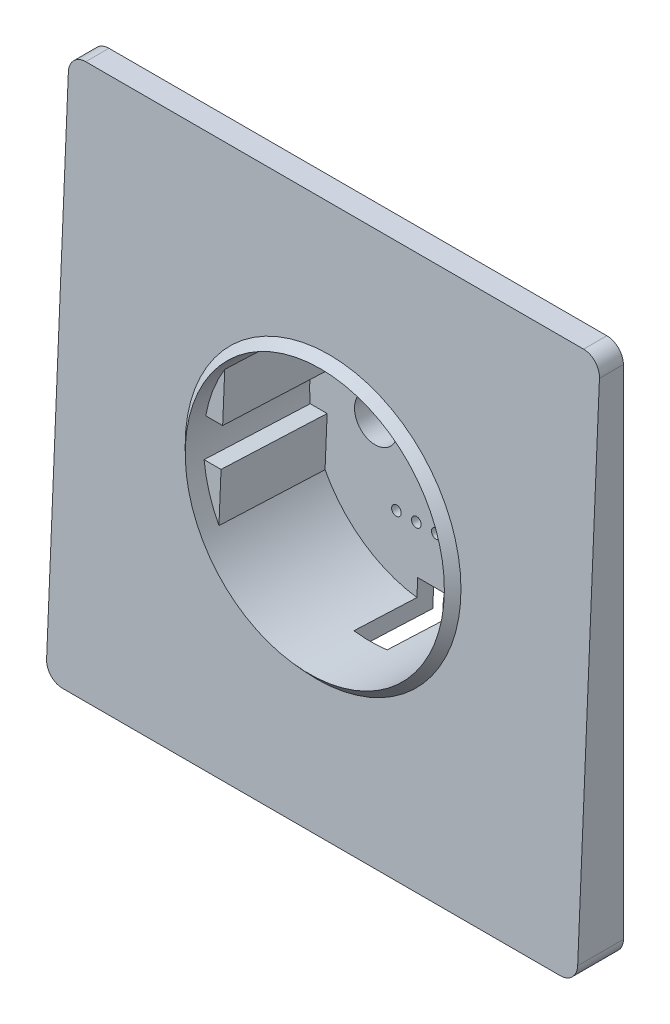
SolidWorks part; units mm, degrees
ref_plane "Ön Düzlem" through (0, 0, 0) normal (0, 0, 1) x (1, 0, 0)
ref_plane "Üst Düzlem" through (0, 0, 0) normal (0, 1, 0) x (1, 0, 0)
ref_plane "Sağ Düzlem" through (0, 0, 0) normal (1, 0, 0) x (0, 0, -1)
sketch "Çizim1" plane through (0, 0, 0) normal (0, 0, 1) x (1, 0, 0)
  line L0 (0, 94.0978) -> (0, -81.5347) construction
  line L1 (-96.2335, 0) -> (117.8421, 0) construction
  line L3 (-37.5, 40) -> (37.5, 40)
  line L4 (-40, 37.5) -> (-40, -37.5)
  line L5 (-37.5, -40) -> (37.5, -40)
  line L6 (40, 37.5) -> (40, -37.5)
  arc A0 (-40, -37.5) -> (-37.5, -40) centre (-37.5, -37.5) ccw
  arc A1 (37.5, -40) -> (40, -37.5) centre (37.5, -37.5) ccw
  arc A2 (37.5, 40) -> (40, 37.5) centre (37.5, 37.5) cw
  arc A3 (-37.5, 40) -> (-40, 37.5) centre (-37.5, 37.5) ccw
  point P17 (-40, 40)
  dimension "D5" = 2.5
  dimension "D1" = 40
  dimension "D2" = 80
  dimension "D3" = 80
  dimension "D4" = 40
extrude "Ekstrüzyon-İnce3" add sketch "Çizim1" along normal blind 7 thin thin type one direction reverse wall 2.5
sketch "Çizim6" plane through (40, 0, 0) normal (1, 0, 0) x (0, 0, -1)
  line L1 (-7, 40) -> (0, 40) construction
  line L2 (-3.5, 40) -> (-7, -40)
  line L3 (-7, -40) -> (-7, 40)
  line L4 (-7, 40) -> (-3.5, 40)
  dimension "D1" = 3.5
extrude "Kes-Ekstrüzyon3" cut sketch "Çizim6" against normal blind 112.5
sketch "Çizim7" plane through (0, 0.2292, 5.24) normal (0, 0.0437, 0.999) x (1, 0, 0)
  line L1 (-38.2758, 38.3418) -> (38.3792, 38.3418)
  line L2 (-38.2758, 38.3418) -> (-38.2758, -38.4901)
  line L3 (-38.2758, -38.4901) -> (38.3792, -38.4901)
  line L4 (38.3792, 38.3418) -> (38.3792, -38.4901)
extrude "Yükseklik-Ekstrüzyon15" add sketch "Çizim7" against normal blind 2.5
sketch "Çizim8" plane through (0, 0.2292, 5.24) normal (0, 0.0437, 0.999) x (1, 0, 0)
  line L0 (0, 29.8509) -> (0, -26.0645) construction
  line L1 (-19.0344, 0) -> (24.7241, 0) construction
  circle A0 centre (0, 0) radius 19.5
  dimension "D1" = 39
extrude "Kes-Ekstrüzyon4" cut sketch "Çizim8" against normal blind 17.5
sketch "Çizim9" plane through (0, 0.2292, 5.24) normal (0, 0.0437, 0.999) x (1, 0, 0)
  circle A0 centre (0, 0) radius 20.75
  dimension "D1" = 41.5
extrude "Yükseklik-Ekstrüzyon16" add sketch "Çizim9" against normal blind 17.5
sketch "Çizim10" plane through (0, 0.2292, 5.24) normal (0, 0.0437, 0.999) x (1, 0, 0)
  circle A0 centre (0, 0) radius 19.5
  dimension "D1" = 39
extrude "Kes-Ekstrüzyon5" cut sketch "Çizim10" against normal blind 17.5
sketch "Çizim11" plane through (0, 0.2292, 5.24) normal (0, 0.0437, 0.999) x (1, 0, 0)
  circle A0 centre (0, 0) radius 20.75
  circle A1 centre (0, 0) radius 19.5
  dimension "D1" = 41.5
  dimension "D2" = 39
extrude "Yükseklik-Ekstrüzyon17" add sketch "Çizim11" along normal blind 1.5
chamfer "Pah1" distance 1.5 angle 45 1 edges at (0, -20.4354, 7.6455)
sketch "Çizim12" plane through (0, -0.5356, -12.2433) normal (0, -0.0437, -0.999) x (-1, 0, 0)
  circle A0 centre (0, 0) radius 20.75
  dimension "D1" = 41.5
extrude "Yükseklik-Ekstrüzyon18" add sketch "Çizim12" along normal blind 2.5
sketch "Çizim13" plane through (0, -0.5356, -12.2433) normal (0, 0.0437, 0.999) x (1, 0, 0)
  line L0 (0, 36.6223) -> (0, -26.6449) construction
  line L1 (7.6552, 0) -> (-11.4827, 0) construction
  circle A0 centre (-9.5, 0) radius 3.25
  circle A1 centre (9.5, 0) radius 3.25
  dimension "D2" = 19
  dimension "D3" = 6.5
  dimension "D4" = 6.5
  dimension "D1" = 9.5
extrude "Kes-Ekstrüzyon7" cut sketch "Çizim13" against normal blind 2.5
sketch "Çizim14" plane through (0, -0.5356, -12.2433) normal (0, 0.0437, 0.999) x (1, 0, 0)
  line L0 (0, 29.0101) -> (0, -24.8666) construction
  line L1 (29.1526, 0) -> (-30.9953, 0) construction
  line L2 (19.2979, 2.8) -> (16.75, 2.8)
  line L3 (16.75, 9.9844) -> (16.75, 2.8)
  line L4 (16.75, -9.9844) -> (16.75, -2.8)
  line L5 (-19.2979, 2.8) -> (-16.75, 2.8)
  line L6 (-16.75, 9.9844) -> (-16.75, 2.8)
  line L7 (19.2979, -2.8) -> (16.75, -2.8)
  line L8 (-16.75, -9.9844) -> (-16.75, -2.8)
  line L9 (-19.2979, -2.8) -> (-16.75, -2.8)
  circle A0 centre (0, 0) radius 19.5
  circle A1 centre (0, 0) radius 19.5 construction
  circle M3 centre (0, 0) radius 19.5
  dimension "D1" = 39
  dimension "D2" = 5.6
  dimension "D4" = 33.5
sketch "Çizim15" plane through (0, -0.5356, -12.2433) normal (0, 0.0437, 0.999) x (1, 0, 0)
  line L0 (0, 34.4478) -> (0, -34.2039) construction
  line L1 (-31.9655, 0) -> (33.3103, 0) construction
  line L2 (2.5, -19.3391) -> (2.5, -16.7891)
  line L3 (-2.5, -16.7891) -> (2.5, -16.7891)
  line L4 (-2.5, 19.3391) -> (-2.5, 16.7891)
  line L5 (-2.5, 16.7891) -> (2.5, 16.7891)
  line L6 (2.5, 19.3391) -> (2.5, 16.7891)
  line L7 (-2.5, -19.3391) -> (-2.5, -16.7891)
  arc A0 (16.75, 9.9844) -> (-16.75, 9.9844) centre (0, 0) ccw construction
  circle A1 centre (0, 0) radius 19.5
  arc M7 (16.75, 9.9844) -> (-16.75, 9.9844) centre (0, 0) ccw
  arc M13 (-16.75, -9.9844) -> (16.75, -9.9844) centre (0, 0) ccw
  dimension "D4" = 39
  dimension "D1" = 2.5
  dimension "D2" = 5
  dimension "D3" = 2.55
extrude "Kes-Ekstrüzyon8" cut sketch "Çizim15" against normal blind 16 contours L6 L4 L5 M7 | L7 L2 L3 M13 region at (0, -18.6365, -11.4514) region at (0, 17.5652, -13.0352)
sketch "Çizim16" plane through (0, -0.6449, -14.7409) normal (0, -0.0437, -0.999) x (-1, 0, 0)
  line L0 (2.5, 16.7891) -> (2.5, 19.3391) construction
  line L1 (-2.5, 16.7891) -> (2.5, 16.7891)
  line L2 (-2.5, 16.7891) -> (-2.5, 21.7891)
  line L3 (-2.5, 21.7891) -> (2.5, 21.7891)
  line L4 (2.5, 16.7891) -> (2.5, 21.7891)
  line L5 (0, 9.913) -> (0, -8.6219) construction
  line L6 (-13.1379, 0) -> (18.1034, 0) construction
  line L7 (-2.5, -16.7891) -> (2.5, -16.7891)
  line L8 (-2.5, -16.7891) -> (-2.5, -21.7891)
  line L9 (-2.5, -21.7891) -> (2.5, -21.7891)
  line L10 (2.5, -16.7891) -> (2.5, -21.7891)
  dimension "D1" = 5
extrude "Kes-Ekstrüzyon10" cut sketch "Çizim16" against normal blind 12
sketch "Çizim17" plane through (0, -0.6449, -14.7409) normal (0, -0.0437, -0.999) x (-1, 0, 0)
  line L0 (0, 10.9316) -> (0, -10.3701) construction
  line L1 (-3.5611, 0) -> (5.2947, 0) construction
  line L3 (-7.5, -8.6891) -> (7.5, -8.6891)
  line L4 (-7.5, -8.6891) -> (-7.5, -11.1891)
  line L5 (-7.5, -11.1891) -> (7.5, -11.1891)
  line L6 (7.5, -8.6891) -> (7.5, -11.1891)
  dimension "D1" = 2.5
  dimension "D2" = 15
  dimension "D3" = 7.5
  dimension "D4" = 5.6
extrude "Yükseklik-Ekstrüzyon21" add sketch "Çizim14" along normal blind 16 contours L6 L5 M3 | L9 L8 M3 | L3 L2 M3 | L7 L4 M3 region at (17.6973, 4.8699, -12.4798) region at (17.6973, -5.9412, -12.0068) region at (-17.6973, 4.8699, -12.4798) region at (-17.6973, -5.9412, -12.0068)
extrude "Kes-Ekstrüzyon14" cut sketch "Çizim17" against normal blind 0.5
sketch "Çizim19" plane through (0, -0.6231, -14.2414) normal (0, -0.0437, -0.999) x (-1, 0, 0)
  line L0 (0, 2.2115) -> (0, -5.0687) construction
  line L2 (-3.7999, 0) -> (16.5883, 0) construction
  line L5 (7.5, -8.6891) -> (-7.5, -8.6891) construction
  line L6 (7.5, -8.6891) -> (-7.5, -8.6891) construction
  circle A0 centre (0, -9.9391) radius 0.725
  circle A1 centre (3, -9.9391) radius 0.725
  circle A2 centre (6, -9.9391) radius 0.725
  circle A3 centre (-3, -9.9391) radius 0.725
  circle A4 centre (-6, -9.9391) radius 0.725
  dimension "D1" = 1.45
  dimension "D3" = 3
  dimension "D5" = 3
  dimension "D6" = 1.25
  dimension "D7" = 3
  dimension "D8" = 1.25
  dimension "D2" = 1.25
  dimension "D4" = 3
extrude "Kes-Ekstrüzyon15" cut sketch "Çizim19" against normal blind 20.5
sketch "Çizim20" plane through (0, -0.6449, -14.7409) normal (0, -0.0437, -0.999) x (-1, 0, 0)
  line L1 (-7.5, -8.6891) -> (7.5, -8.6891)
  line L2 (-7.5, -8.6891) -> (-7.5, -11.1891)
  line L3 (-7.5, -11.1891) -> (7.5, -11.1891)
  line L4 (7.5, -8.6891) -> (7.5, -11.1891)
  line L5 (-8.5, -7.6891) -> (8.5, -7.6891)
  line L6 (-8.5, -7.6891) -> (-8.5, -12.1891)
  line L7 (-8.5, -12.1891) -> (8.5, -12.1891)
  line L8 (8.5, -7.6891) -> (8.5, -12.1891)
  dimension "D1" = 1
  dimension "D2" = 1
  dimension "D3" = 1
  dimension "D4" = 1
extrude "Yükseklik-Ekstrüzyon23" add sketch "Çizim20" along normal blind 1
sketch "Çizim22" plane through (0, -0.6449, -14.7409) normal (0, -0.0437, -0.999) x (-1, 0, 0)
  circle A0 centre (-9.5, 0) radius 4.25
  circle A1 centre (9.5, 0) radius 4.25
  circle A4 centre (-9.5, 0) radius 3.25
  circle A5 centre (9.5, 0) radius 3.25
  dimension "D1" = 8.5
  dimension "D2" = 8.5
  dimension "D3" = 6.5
  dimension "D4" = 6.5
extrude "Yükseklik-Ekstrüzyon26" add sketch "Çizim22" along normal blind 2.5
sketch "Çizim26" plane through (0, -0.6449, -14.7409) normal (0, -0.0437, -0.999) x (-1, 0, 0)
  line L0 (0, 9.3055) -> (0, -4.9493) construction
  line L1 (-2.5955, 0) -> (18.607, 0) construction
  line L2 (-9.5, 3.25) -> (-9.5, 0) construction
  line L3 (9.5, 3.25) -> (9.5, 0) construction
  line L4 (-8, -8.9765) -> (-8, -3.9765)
  line L5 (-10, 9.9765) -> (-9, 9.9765)
  line L6 (-11, 8.9765) -> (-11, 3.9765)
  line L7 (-11, -8.9765) -> (-11, -3.9765)
  line L8 (-8, 8.9765) -> (-8, 3.9765)
  line L9 (-10, -9.9765) -> (-9, -9.9765)
  line L10 (10, -9.9765) -> (9, -9.9765)
  line L11 (8, 8.9765) -> (8, 3.9765)
  line L12 (11, -8.9765) -> (11, -3.9765)
  line L13 (11, 8.9765) -> (11, 3.9765)
  line L14 (10, 9.9765) -> (9, 9.9765)
  line L15 (8, -8.9765) -> (8, -3.9765)
  arc A0 (-10, -9.9765) -> (-11, -8.9765) centre (-10, -8.9765) cw
  arc A1 (-9, -9.9765) -> (-8, -8.9765) centre (-9, -8.9765) ccw
  circle A2 centre (-9.5, 0) radius 4.25
  arc A3 (-9, 9.9765) -> (-8, 8.9765) centre (-9, 8.9765) cw
  arc A4 (-10, 9.9765) -> (-11, 8.9765) centre (-10, 8.9765) ccw
  arc A5 (10, 9.9765) -> (11, 8.9765) centre (10, 8.9765) cw
  arc A6 (9, 9.9765) -> (8, 8.9765) centre (9, 8.9765) ccw
  circle A7 centre (9.5, 0) radius 4.25
  arc A8 (9, -9.9765) -> (8, -8.9765) centre (9, -8.9765) cw
  arc A9 (10, -9.9765) -> (11, -8.9765) centre (10, -8.9765) ccw
  point P22 (-11, 9.9765)
  point P29 (-11, -9.9765)
  point P48 (11, -9.9765)
  point P49 (11, 9.9765)
  circle M1 centre (-9.5, 0) radius 4.25
  line M11 (-8.5, -12.1891) -> (-8.5, -7.6891)
  line M12 (-8.5, -7.6891) -> (8.5, -7.6891)
  line M13 (8.5, -7.6891) -> (8.5, -12.1891)
  circle M14 centre (9.5, 0) radius 4.25
  dimension "D3" = 8.5
  dimension "D5" = 1
  dimension "D1" = 1.5
  dimension "D2" = 3
  dimension "D4" = 6
extrude "Yükseklik-Ekstrüzyon27" add sketch "Çizim26" along normal blind 13 contours L5 A4 L6 L8 A3 M1 | L14 A6 L11 L13 A5 M14 | L10 A9 L12 L15 A8 M14 M12 M13 | L9 A1 L4 L7 A0 M11 M12 M1 region at (-9.5731, -7.5407, -14.4392) region at (9.5731, -7.5407, -14.4392) region at (9.5, 6.3484, -15.0469) region at (-9.5, 6.3484, -15.0469)
sketch "Çizim27" plane through (0, -1.2131, -27.7285) normal (0, -0.0437, -0.999) x (-1, 0, 0)
  line L0 (0, 15.1334) -> (0, -5.1774) construction
  line L1 (3.8521, 0) -> (-3.9673, 0) construction
  line L2 (-10, 9.9765) -> (-9, 9.9765)
  line L3 (-10, 9.9765) -> (-10, 4.1985)
  line L4 (-9, 9.9765) -> (-9, 4.1985)
  line L5 (-10, 4.1985) -> (-9, 4.1985)
  line L6 (10, 4.1985) -> (9, 4.1985)
  line L7 (9, 9.9765) -> (9, 4.1985)
  line L8 (10, 9.9765) -> (10, 4.1985)
  line L9 (10, 9.9765) -> (9, 9.9765)
  line L10 (10, -9.9765) -> (9, -9.9765)
  line L11 (10, -9.9765) -> (10, -4.1985)
  line L12 (9, -9.9765) -> (9, -4.1985)
  line L13 (10, -4.1985) -> (9, -4.1985)
  line L14 (-10, -4.1985) -> (-9, -4.1985)
  line L15 (-9, -9.9765) -> (-9, -4.1985)
  line L16 (-10, -9.9765) -> (-10, -4.1985)
  line L17 (-10, -9.9765) -> (-9, -9.9765)
extrude "Kes-Ekstrüzyon18" cut sketch "Çizim27" against normal blind 4
sketch "Çizim31" plane through (0, -12.1774, 0.5328) normal (0, -0.999, 0.0437) x (1, 0, 0)
  line L0 (0, 0) -> (0, -22.981) construction
  line L1 (0, -15.755) -> (15.5795, -15.755) construction
  circle A0 centre (0, -15.755) radius 0.725
  circle A1 centre (3, -15.755) radius 0.725
  circle A2 centre (6, -15.755) radius 0.725
  circle A3 centre (-3, -15.755) radius 0.725
  circle A4 centre (-6, -15.755) radius 0.725
  dimension "D1" = 1.45
  dimension "D3" = 3
  dimension "D5" = 3
  dimension "D4" = 3
  dimension "D2" = 3
extrude "Kes-Ekstrüzyon19" cut sketch "Çizim31" against normal blind 5
chamfer "Pah5" distance 1 angle 45 20 edges at (-8, -6.4721, -14.486) (8.7412, -10.5778, -14.3064) (9.5, -10.6119, -14.3049) (11, -7.1152, -14.4578) (10.7071, -10.3193, -14.3177) (8, -6.4721, -14.486) (11, 5.8254, -15.024) (10.7071, 9.0294, -15.1642) (9.5, 9.322, -15.177) (8, 5.8254, -15.024) (8.2929, 9.0294, -15.1642) (-8, 5.8254, -15.024) (-8.2929, 9.0294, -15.1642) (-9.5, 9.322, -15.177) (-10.7071, 9.0294, -15.1642) (-11, 5.8254, -15.024) (-8.7412, -10.5778, -14.3064) (-9.5, -10.6119, -14.3049) (-11, -7.1152, -14.4578) (-10.7071, -10.3193, -14.3177)
sketch "Çizim32" plane through (0, -0.6449, -14.7409) normal (0, -0.0437, -0.999) x (-1, 0, 0)
  line L0 (0, 8.6833) -> (0, -3.8675) construction
  line L1 (0, 0) -> (4.7888, 0) construction
  circle A0 centre (0, 0) radius 3.25
  circle A1 centre (0, 0) radius 0.75
  dimension "D1" = 6.5
  dimension "D2" = 1.5
extrude "Yükseklik-Ekstrüzyon29" add sketch "Çizim32" along normal blind 13
ref_plane "Düzlem2" through (0, -37.5, 0) normal (0, 1, 0) x (1, 0, 0)
sketch "Çizim37" plane through (0, -37.5, 0) normal (0, 1, 0) x (1, 0, 0)
  line L0 (0, 0) -> (0, -6.3762) construction
  line L1 (-37.5, 0) -> (37.5, 0) construction
  line L2 (22, 0) -> (18.6341, -3.4753)
  line L3 (-22, 0) -> (-18.6341, -3.4753)
  line L4 (-22, 0) -> (22, 0)
  line L5 (-37.5, -4.3882) -> (37.5, -4.3882) construction
  line L6 (16.4791, -4.3882) -> (-16.4791, -4.3882)
  arc A0 (-18.6341, -3.4753) -> (-16.4791, -4.3882) centre (-16.4791, -1.3882) ccw
  arc A1 (18.6341, -3.4753) -> (16.4791, -4.3882) centre (16.4791, -1.3882) cw
  point P10 (0, -4.3882)
  point P12 (0, 0)
  point P14 (-17.75, -4.3882)
  point P17 (17.75, -4.3882)
  dimension "D3" = 3
  dimension "D1" = 4.25
  dimension "D2" = 22
extrude "Kes-Ekstrüzyon29" cut sketch "Çizim37" against normal blind 21
sketch "Çizim40" plane through (0, -37.5, 0) normal (0, 1, 0) x (1, 0, 0)
  line L0 (16.4791, -4.3882) -> (37.5, -4.3882) construction
  line L1 (26, -4.3882) -> (-26, -4.3882)
  line L2 (26, -4.3882) -> (26, 0)
  line L3 (26, 0) -> (-26, 0)
  line L4 (-26, -4.3882) -> (-26, 0)
  line L5 (-37.5, 0) -> (-22, 0) construction
  line L6 (0, 0.2626) -> (0, 12.1609) construction
  dimension "D1" = 26
  dimension "D2" = 52
extrude "Kes-Ekstrüzyon30" cut sketch "Çizim40" against normal blind 0.9
sketch "Çizim45" plane through (0, 0.12, 2.7424) normal (0, -0.0437, -0.999) x (-1, 0, 0)
  circle A0 centre (0, 0) radius 22
  circle A1 centre (0, 0) radius 20.75
  dimension "D1" = 44
extrude "Yükseklik-Ekstrüzyon31" add sketch "Çizim45" along normal blind 17.5
sketch "Çizim46" plane through (0, -0.6449, -14.7409) normal (0, -0.0437, -0.999) x (-1, 0, 0)
  line L1 (-2.5, 16.7891) -> (2.5, 16.7891)
  line L2 (-2.5, 16.7891) -> (-2.5, 24.6685)
  line L3 (-2.5, 24.6685) -> (2.5, 24.6685)
  line L4 (2.5, 16.7891) -> (2.5, 24.6685)
  line L5 (2.5, 16.7891) -> (2.5, 20.5988) construction
  line L6 (0, 0) -> (-34.6436, 0) construction
  line L8 (2.5, -16.7891) -> (2.5, -24.6685)
  line L9 (-2.5, -24.6685) -> (2.5, -24.6685)
  line L10 (-2.5, -16.7891) -> (-2.5, -24.6685)
  line L11 (-2.5, -16.7891) -> (2.5, -16.7891)
extrude "Kes-Ekstrüzyon32" cut sketch "Çizim46" against normal blind 12
